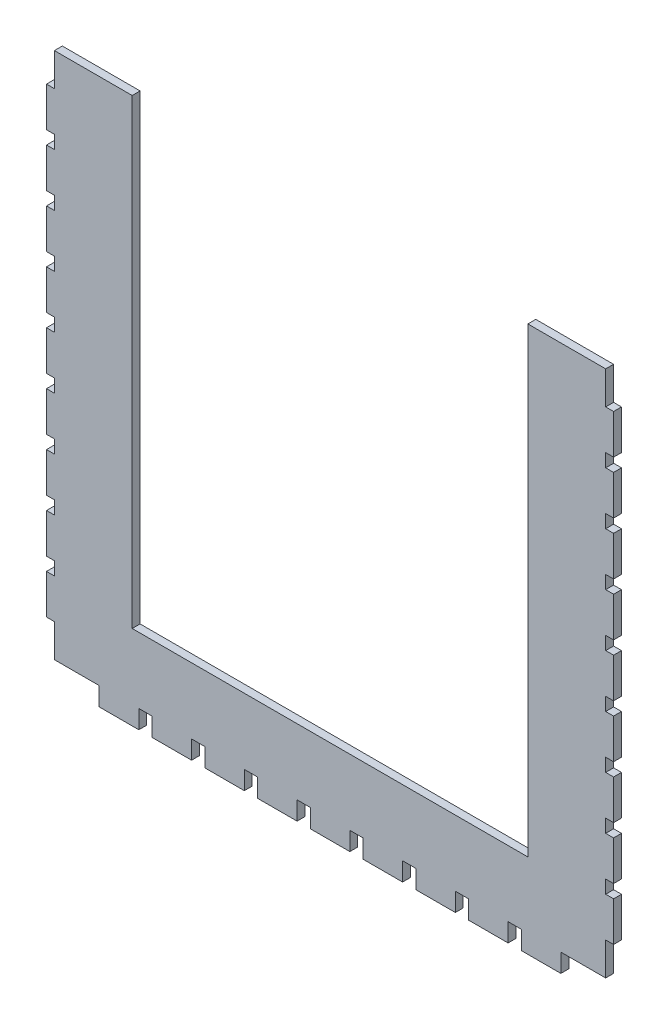
SolidWorks part; units mm, degrees
material "Nickel"
ref_plane "Front Plane" through (0, 0, 0) normal (0, 0, 1) x (1, 0, 0)
ref_plane "Top Plane" through (0, 0, 0) normal (0, 1, 0) x (1, 0, 0)
ref_plane "Right Plane" through (0, 0, 0) normal (1, 0, 0) x (0, 0, -1)
sketch "Sketch1" plane through (0, 0, 0) normal (0, 0, 1) x (1, 0, 0)
  line L0 (-104.5, 100) -> (-104.5, -100)
  line L3 (-104.5, 100) -> (104.5, 100)
  line L4 (104.5, -100) -> (104.5, 100)
  line L5 (-104.5, -100) -> (104.5, -100)
  line L6 (0, 100) -> (0, -100) construction
  line L7 (-104.5, 0) -> (104.5, 0) construction
  line L8 (107.5, 0) -> (104.5, 0) construction
  line L9 (-75, 100) -> (75, 100)
  line L10 (-75, 100) -> (-75, -75)
  line L11 (-75, -75) -> (75, -75)
  line L12 (75, 100) -> (75, -75)
  line L15 (104.5, 7.5) -> (107.5, 7.5)
  line L16 (104.5, 7.5) -> (104.5, -7.5)
  line L17 (104.5, -7.5) -> (107.5, -7.5)
  line L18 (107.5, 7.5) -> (107.5, -7.5)
  line L19 (106, 7.5) -> (106, -7.5) construction
  line L20 (104.5, -12.5) -> (104.5, -27.5)
  line L21 (104.5, -12.5) -> (107.5, -12.5)
  line L22 (107.5, -12.5) -> (107.5, -27.5)
  line L23 (104.5, -27.5) -> (107.5, -27.5)
  line L24 (104.5, -32.5) -> (104.5, -47.5)
  line L25 (104.5, -32.5) -> (107.5, -32.5)
  line L26 (107.5, -32.5) -> (107.5, -47.5)
  line L27 (104.5, -47.5) -> (107.5, -47.5)
  line L28 (104.5, -52.5) -> (104.5, -67.5)
  line L29 (104.5, -52.5) -> (107.5, -52.5)
  line L30 (107.5, -52.5) -> (107.5, -67.5)
  line L31 (104.5, -67.5) -> (107.5, -67.5)
  line L32 (104.5, -72.5) -> (104.5, -87.5)
  line L33 (104.5, -72.5) -> (107.5, -72.5)
  line L34 (107.5, -72.5) -> (107.5, -87.5)
  line L35 (104.5, -87.5) -> (107.5, -87.5)
  line L36 (104.5, 27.5) -> (104.5, 12.5)
  line L37 (104.5, 27.5) -> (107.5, 27.5)
  line L38 (107.5, 27.5) -> (107.5, 12.5)
  line L39 (104.5, 12.5) -> (107.5, 12.5)
  line L40 (104.5, 47.5) -> (104.5, 32.5)
  line L41 (104.5, 47.5) -> (107.5, 47.5)
  line L42 (107.5, 47.5) -> (107.5, 32.5)
  line L43 (104.5, 32.5) -> (107.5, 32.5)
  line L44 (104.5, 67.5) -> (104.5, 52.5)
  line L45 (104.5, 67.5) -> (107.5, 67.5)
  line L46 (107.5, 67.5) -> (107.5, 52.5)
  line L47 (104.5, 52.5) -> (107.5, 52.5)
  line L48 (104.5, 87.5) -> (104.5, 72.5)
  line L49 (104.5, 87.5) -> (107.5, 87.5)
  line L50 (107.5, 87.5) -> (107.5, 72.5)
  line L51 (104.5, 72.5) -> (107.5, 72.5)
  line L52 (-104.5, -32.5) -> (-107.5, -32.5)
  line L53 (-107.5, -32.5) -> (-107.5, -47.5)
  line L54 (-104.5, -47.5) -> (-107.5, -47.5)
  line L55 (-104.5, -32.5) -> (-104.5, -47.5)
  line L56 (-104.5, -52.5) -> (-107.5, -52.5)
  line L57 (-107.5, -52.5) -> (-107.5, -67.5)
  line L58 (-104.5, -67.5) -> (-107.5, -67.5)
  line L59 (-104.5, -52.5) -> (-104.5, -67.5)
  line L60 (-104.5, 87.5) -> (-107.5, 87.5)
  line L61 (-107.5, 87.5) -> (-107.5, 72.5)
  line L62 (-104.5, 72.5) -> (-107.5, 72.5)
  line L63 (-104.5, 87.5) -> (-104.5, 72.5)
  line L64 (-104.5, 67.5) -> (-107.5, 67.5)
  line L65 (-107.5, 67.5) -> (-107.5, 52.5)
  line L66 (-104.5, 52.5) -> (-107.5, 52.5)
  line L67 (-104.5, 67.5) -> (-104.5, 52.5)
  line L68 (-104.5, 47.5) -> (-107.5, 47.5)
  line L69 (-107.5, 47.5) -> (-107.5, 32.5)
  line L70 (-104.5, 32.5) -> (-107.5, 32.5)
  line L71 (-104.5, 47.5) -> (-104.5, 32.5)
  line L72 (-104.5, 27.5) -> (-107.5, 27.5)
  line L73 (-107.5, 27.5) -> (-107.5, 12.5)
  line L74 (-104.5, 12.5) -> (-107.5, 12.5)
  line L75 (-104.5, 27.5) -> (-104.5, 12.5)
  line L76 (-104.5, -12.5) -> (-107.5, -12.5)
  line L77 (-107.5, -12.5) -> (-107.5, -27.5)
  line L78 (-104.5, -27.5) -> (-107.5, -27.5)
  line L79 (-104.5, -12.5) -> (-104.5, -27.5)
  line L80 (-104.5, -7.5) -> (-107.5, -7.5)
  line L81 (-107.5, 7.5) -> (-107.5, -7.5)
  line L82 (-104.5, 7.5) -> (-107.5, 7.5)
  line L83 (-104.5, 7.5) -> (-104.5, -7.5)
  line L84 (-104.5, -87.5) -> (-107.5, -87.5)
  line L85 (-107.5, -72.5) -> (-107.5, -87.5)
  line L86 (-104.5, -72.5) -> (-107.5, -72.5)
  line L87 (-104.5, -72.5) -> (-104.5, -87.5)
  line L88 (0, -100) -> (0, -107) construction
  line L89 (-7.5, -100) -> (7.5, -100)
  line L90 (-7.5, -100) -> (-7.5, -107)
  line L91 (-7.5, -107) -> (7.5, -107)
  line L92 (7.5, -100) -> (7.5, -107)
  line L93 (12.5, -100) -> (12.5, -107)
  line L94 (-7.5, -103.5) -> (7.5, -103.5) construction
  line L95 (12.5, -100) -> (27.5, -100)
  line L96 (27.5, -100) -> (27.5, -107)
  line L97 (12.5, -107) -> (27.5, -107)
  line L98 (32.5, -100) -> (32.5, -107)
  line L99 (32.5, -100) -> (47.5, -100)
  line L100 (47.5, -100) -> (47.5, -107)
  line L101 (32.5, -107) -> (47.5, -107)
  line L102 (52.5, -100) -> (52.5, -107)
  line L103 (52.5, -100) -> (67.5, -100)
  line L104 (67.5, -100) -> (67.5, -107)
  line L105 (52.5, -107) -> (67.5, -107)
  line L106 (72.5, -100) -> (72.5, -107)
  line L107 (72.5, -100) -> (87.5, -100)
  line L108 (87.5, -100) -> (87.5, -107)
  line L109 (72.5, -107) -> (87.5, -107)
  line L110 (-7.5, -100) -> (-7.5, -107)
  line L111 (-7.5, -100) -> (7.5, -100)
  line L112 (7.5, -100) -> (7.5, -107)
  line L113 (-7.5, -107) -> (7.5, -107)
  line L114 (12.5, -100) -> (12.5, -107)
  line L115 (12.5, -100) -> (27.5, -100)
  line L116 (27.5, -100) -> (27.5, -107)
  line L117 (12.5, -107) -> (27.5, -107)
  line L118 (32.5, -100) -> (32.5, -107)
  line L119 (32.5, -100) -> (47.5, -100)
  line L120 (47.5, -100) -> (47.5, -107)
  line L121 (32.5, -107) -> (47.5, -107)
  line L122 (52.5, -100) -> (52.5, -107)
  line L123 (52.5, -100) -> (67.5, -100)
  line L124 (67.5, -100) -> (67.5, -107)
  line L125 (52.5, -107) -> (67.5, -107)
  line L126 (-27.5, -100) -> (-27.5, -107)
  line L127 (-27.5, -100) -> (-12.5, -100)
  line L128 (-12.5, -100) -> (-12.5, -107)
  line L129 (-27.5, -107) -> (-12.5, -107)
  line L130 (-7.5, -100) -> (-7.5, -107)
  line L131 (-7.5, -100) -> (7.5, -100)
  line L132 (7.5, -100) -> (7.5, -107)
  line L133 (-7.5, -107) -> (7.5, -107)
  line L134 (12.5, -100) -> (12.5, -107)
  line L135 (12.5, -100) -> (27.5, -100)
  line L136 (27.5, -100) -> (27.5, -107)
  line L137 (12.5, -107) -> (27.5, -107)
  line L138 (32.5, -100) -> (32.5, -107)
  line L139 (32.5, -100) -> (47.5, -100)
  line L140 (47.5, -100) -> (47.5, -107)
  line L141 (32.5, -107) -> (47.5, -107)
  line L142 (-47.5, -100) -> (-47.5, -107)
  line L143 (-47.5, -100) -> (-32.5, -100)
  line L144 (-32.5, -100) -> (-32.5, -107)
  line L145 (-47.5, -107) -> (-32.5, -107)
  line L146 (-27.5, -100) -> (-27.5, -107)
  line L147 (-27.5, -100) -> (-12.5, -100)
  line L148 (-12.5, -100) -> (-12.5, -107)
  line L149 (-27.5, -107) -> (-12.5, -107)
  line L150 (-7.5, -100) -> (-7.5, -107)
  line L151 (-7.5, -100) -> (7.5, -100)
  line L152 (7.5, -100) -> (7.5, -107)
  line L153 (-7.5, -107) -> (7.5, -107)
  line L154 (12.5, -100) -> (12.5, -107)
  line L155 (12.5, -100) -> (27.5, -100)
  line L156 (27.5, -100) -> (27.5, -107)
  line L157 (12.5, -107) -> (27.5, -107)
  line L158 (-67.5, -100) -> (-67.5, -107)
  line L159 (-67.5, -100) -> (-52.5, -100)
  line L160 (-52.5, -100) -> (-52.5, -107)
  line L161 (-67.5, -107) -> (-52.5, -107)
  line L162 (-47.5, -100) -> (-47.5, -107)
  line L163 (-47.5, -100) -> (-32.5, -100)
  line L164 (-32.5, -100) -> (-32.5, -107)
  line L165 (-47.5, -107) -> (-32.5, -107)
  line L166 (-27.5, -100) -> (-27.5, -107)
  line L167 (-27.5, -100) -> (-12.5, -100)
  line L168 (-12.5, -100) -> (-12.5, -107)
  line L169 (-27.5, -107) -> (-12.5, -107)
  line L170 (-7.5, -100) -> (-7.5, -107)
  line L171 (-7.5, -100) -> (7.5, -100)
  line L172 (7.5, -100) -> (7.5, -107)
  line L173 (-7.5, -107) -> (7.5, -107)
  line L174 (-27.5, -100) -> (-27.5, -107)
  line L175 (-27.5, -100) -> (-12.5, -100)
  line L176 (-12.5, -100) -> (-12.5, -107)
  line L177 (-27.5, -107) -> (-12.5, -107)
  line L178 (-47.5, -100) -> (-47.5, -107)
  line L179 (-47.5, -100) -> (-32.5, -100)
  line L180 (-32.5, -100) -> (-32.5, -107)
  line L181 (-47.5, -107) -> (-32.5, -107)
  line L182 (-67.5, -100) -> (-67.5, -107)
  line L183 (-67.5, -100) -> (-52.5, -100)
  line L184 (-52.5, -100) -> (-52.5, -107)
  line L185 (-67.5, -107) -> (-52.5, -107)
  line L186 (-87.5, -100) -> (-87.5, -107)
  line L187 (-87.5, -100) -> (-72.5, -100)
  line L188 (-72.5, -100) -> (-72.5, -107)
  line L189 (-87.5, -107) -> (-72.5, -107)
  point P0 (0, 0)
  point P11 (0, 0)
  point P12 (0, 0)
  point P21 (106, 12.5)
  dimension "D1" = 200
  dimension "D2" = 209
  dimension "D3" = 75
  dimension "D4" = 150
  dimension "D5" = 3
  dimension "D6" = 15
  dimension "D9" = 5
  dimension "D10" = 5
  dimension "D11" = 15
  dimension "D12" = 7
  dimension "D15" = 5
  dimension "D16" = 5
  dimension "D17" = 100
  dimension "D18" = 75
  dimension "D7" = 5
  dimension "D8" = 5
  dimension "D13" = 5
  dimension "D14" = 5
extrude "Boss-Extrude1" add sketch "Sketch1" along normal blind 3 contours L0 L5 L4 | L186 L189 L188 L5 | L158 L161 L160 L5 | L142 L145 L144 L5 | L126 L129 L128 L5 | L92 L5 L90 L91 | L93 L97 L96 L5 | L98 L101 L100 L5 | L106 L109 L108 L5 | L4 L35 L34 L33 | L4 L31 L30 L29 | L4 L27 L26 L25 | L4 L23 L22 L21 | L4 L39 L38 L37 | L4 L47 L46 L45 | L4 L51 L50 L49 | L62 L0 L60 L61 | L66 L0 L64 L65 | L70 L0 L68 L69 | L74 L0 L72 L73 | L0 L82 L81 L80 | L78 L0 L76 L77 | L54 L0 L52 L53 | L58 L0 L56 L57 | L0 L86 L85 L84 | L42 L43 L40 L41 | L102 L105 L104 L103 | L16 L15 L18 L17 region at (-89.75, 97.1072, 0) region at (-106, 80, 0) region at (-106, 60, 0) region at (106, 80, 0) region at (-106, 40, 0) region at (106, 60, 0) region at (-106, 20, 0) region at (-106, 0, 0) region at (106, 20, 0) region at (-106, -20, 0) region at (-106, -40, 0) region at (106, -20, 0) region at (-106, -60, 0) region at (106, -40, 0) region at (-106, -80, 0) region at (106, -60, 0) region at (-80, -103.5, 0) region at (106, -80, 0) region at (-60, -103.5, 0) region at (80, -103.5, 0) region at (-40, -103.5, 0) region at (-20, -103.5, 0) region at (40, -103.5, 0) region at (0, -103.5, 0) region at (20, -103.5, 0)
sketch "Sketch3" plane through (0, -75, 0) normal (0, 1, 0) x (1, 0, 0)
  line L1 (-75, -3) -> (75, -3)
  line L2 (-75, -3) -> (-75, 0)
  line L3 (-75, 0) -> (75, 0)
  line L4 (75, -3) -> (75, 0)
extrude "Boss-Extrude2" [suppressed] add sketch "Sketch3" along normal blind 150
sketch "Sketch5" [suppressed] plane through (0, 0, 3) normal (0, 0, 1) x (1, 0, 0)
  line L0 (0, 0) -> (0, -80.2869) construction
  line L6 (0, -14.4991) -> (12.5, -7.1524)
  line L7 (12.5, -7.1524) -> (12.5, 6.8326)
  line L8 (12.5, 6.8326) -> (0, 14.8505)
  line L9 (0, 14.8505) -> (-12.5, 6.8326)
  line L10 (-12.5, 6.8326) -> (-12.5, -7.1524)
  line L11 (-12.5, -7.1524) -> (0, -14.4991)
  line L12 (-17.5, 11.8326) -> (-5, 19.1793)
  line L13 (-5, 19.1793) -> (-5, 33.1643)
  line L14 (-5, 33.1643) -> (-17.5, 41.1822)
  line L15 (-17.5, 41.1822) -> (-30, 33.1643)
  line L16 (-30, 33.1643) -> (-30, 19.1793)
  line L17 (-30, 19.1793) -> (-17.5, 11.8326)
  line L18 (17.5, 11.8326) -> (30, 19.1793)
  line L19 (30, 19.1793) -> (30, 33.1643)
  line L20 (30, 33.1643) -> (17.5, 41.1822)
  line L21 (17.5, 41.1822) -> (5, 33.1643)
  line L22 (5, 33.1643) -> (5, 19.1793)
  line L23 (5, 19.1793) -> (17.5, 11.8326)
  line L24 (-35, 38.1643) -> (-22.5, 45.511)
  line L25 (-22.5, 45.511) -> (-22.5, 59.496)
  line L26 (-22.5, 59.496) -> (-35, 67.5139)
  line L27 (-35, 67.5139) -> (-47.5, 59.496)
  line L28 (-47.5, 59.496) -> (-47.5, 45.511)
  line L29 (-47.5, 45.511) -> (-35, 38.1643)
  line L30 (0, 38.1643) -> (12.5, 45.511)
  line L31 (12.5, 45.511) -> (12.5, 59.496)
  line L32 (12.5, 59.496) -> (0, 67.5139)
  line L33 (0, 67.5139) -> (-12.5, 59.496)
  line L34 (-12.5, 59.496) -> (-12.5, 45.511)
  line L35 (-12.5, 45.511) -> (0, 38.1643)
  line L36 (35, 38.1643) -> (47.5, 45.511)
  line L37 (47.5, 45.511) -> (47.5, 59.496)
  line L38 (47.5, 59.496) -> (35, 67.5139)
  line L39 (35, 67.5139) -> (22.5, 59.496)
  line L40 (22.5, 59.496) -> (22.5, 45.511)
  line L41 (22.5, 45.511) -> (35, 38.1643)
  line L42 (-90, 0) -> (90, 0) construction
  line L43 (0, 0) -> (0, 84.5664) construction
  line L44 (-107.5, -72.5) -> (-107.5, -87.5) construction
  line L45 (90, 26.3317) -> (-90, 26.3317) construction
  line L46 (-87.5, -107) -> (-72.5, -107) construction
  line L47 (-17.5, -41.1506) -> (-5, -33.8039)
  line L48 (-5, -33.8039) -> (-5, -19.4991)
  line L49 (-5, -19.4991) -> (-17.5, -12.1524)
  line L50 (-17.5, -12.1524) -> (-30, -19.4991)
  line L51 (-30, -19.4991) -> (-30, -33.8039)
  line L52 (-30, -33.8039) -> (-17.5, -41.1506)
  line L53 (17.5, -41.1506) -> (30, -33.8039)
  line L54 (30, -33.8039) -> (30, -19.4991)
  line L55 (30, -19.4991) -> (17.5, -12.1524)
  line L56 (17.5, -12.1524) -> (5, -19.4991)
  line L57 (5, -19.4991) -> (5, -33.8039)
  line L58 (5, -33.8039) -> (17.5, -41.1506)
  line L59 (-35, -67.8021) -> (-22.5, -60.4554)
  line L60 (-22.5, -60.4554) -> (-22.5, -46.1506)
  line L61 (-22.5, -46.1506) -> (-35, -38.8039)
  line L62 (-35, -38.8039) -> (-47.5, -46.1506)
  line L63 (-47.5, -46.1506) -> (-47.5, -60.4554)
  line L64 (-47.5, -60.4554) -> (-35, -67.8021)
  line L65 (0, -67.8021) -> (12.5, -60.4554)
  line L66 (12.5, -60.4554) -> (12.5, -46.1506)
  line L67 (12.5, -46.1506) -> (0, -38.8039)
  line L68 (0, -38.8039) -> (-12.5, -46.1506)
  line L69 (-12.5, -46.1506) -> (-12.5, -60.4554)
  line L70 (-12.5, -60.4554) -> (0, -67.8021)
  line L71 (35, -67.8021) -> (47.5, -60.4554)
  line L72 (47.5, -60.4554) -> (47.5, -46.1506)
  line L73 (47.5, -46.1506) -> (35, -38.8039)
  line L74 (35, -38.8039) -> (22.5, -46.1506)
  line L75 (22.5, -46.1506) -> (22.5, -60.4554)
  line L76 (22.5, -60.4554) -> (35, -67.8021)
  line L77 (35, -14.4991) -> (47.5, -7.1524)
  line L78 (47.5, -7.1524) -> (47.5, 7.1524)
  line L79 (47.5, 7.1524) -> (35, 14.4991)
  line L80 (35, 14.4991) -> (22.5, 7.1524)
  line L81 (22.5, 7.1524) -> (22.5, -7.1524)
  line L82 (22.5, -7.1524) -> (35, -14.4991)
  line L83 (-35, -14.4991) -> (-22.5, -7.1524)
  line L84 (-22.5, -7.1524) -> (-22.5, 7.1524)
  line L85 (-22.5, 7.1524) -> (-35, 14.4991)
  line L86 (-35, 14.4991) -> (-47.5, 7.1524)
  line L87 (-47.5, 7.1524) -> (-47.5, -7.1524)
  line L88 (-47.5, -7.1524) -> (-35, -14.4991)
  line L89 (-17.5, -94.4537) -> (-5, -87.1069)
  line L90 (-5, -87.1069) -> (-5, -72.8021)
  line L91 (-5, -72.8021) -> (-17.5, -65.4554)
  line L92 (-17.5, -65.4554) -> (-30, -72.8021)
  line L93 (-30, -72.8021) -> (-30, -87.1069)
  line L94 (-30, -87.1069) -> (-17.5, -94.4537)
  line L95 (17.5, -94.4537) -> (30, -87.1069)
  line L96 (30, -87.1069) -> (30, -72.8021)
  line L97 (30, -72.8021) -> (17.5, -65.4554)
  line L98 (17.5, -65.4554) -> (5, -72.8021)
  line L99 (5, -72.8021) -> (5, -87.1069)
  line L100 (5, -87.1069) -> (17.5, -94.4537)
  circle A0 centre (0, 0) radius 12.5 construction
  circle A1 centre (-17.5, 26.3317) radius 12.5 construction
  circle A2 centre (17.5, 26.3317) radius 12.5 construction
  circle A3 centre (-35, 52.6634) radius 12.5 construction
  circle A4 centre (0, 52.6634) radius 12.5 construction
  circle A5 centre (35, 52.6634) radius 12.5 construction
  circle A6 centre (-17.5, -26.6515) radius 12.5 construction
  circle A7 centre (17.5, -26.6515) radius 12.5 construction
  circle A8 centre (-35, -53.303) radius 12.5 construction
  circle A9 centre (0, -53.303) radius 12.5 construction
  circle A10 centre (35, -53.303) radius 12.5 construction
  circle A11 centre (35, 0) radius 12.5 construction
  circle A12 centre (-35, 0) radius 12.5 construction
  circle A13 centre (-17.5, -79.9545) radius 12.5 construction
  circle A14 centre (17.5, -79.9545) radius 12.5 construction
  dimension "D11" = 25
  dimension "D12" = 25
  dimension "D13" = 25
  dimension "D14" = 25
  dimension "D15" = 25
  dimension "D16" = 26.3317
  dimension "D23" = 25
  dimension "D24" = 25
  dimension "D25" = 25
  dimension "D26" = 25
  dimension "D27" = 25
  dimension "D29" = 25
  dimension "D30" = 25
  dimension "D31" = 25
  dimension "D32" = 25
  dimension "D4" = 5
  dimension "D5" = 5
  dimension "D6" = 5
  dimension "D7" = 5
  dimension "D8" = 5
  dimension "D9" = 5
  dimension "D10" = 5
  dimension "D17" = 35
  dimension "D18" = 34.5
  dimension "D19" = 23.6652
  dimension "D22" = 5
  dimension "D28" = 5
  dimension "D33" = 5
extrude "Cut-Extrude1" [suppressed] cut sketch "Sketch5" against normal through all
